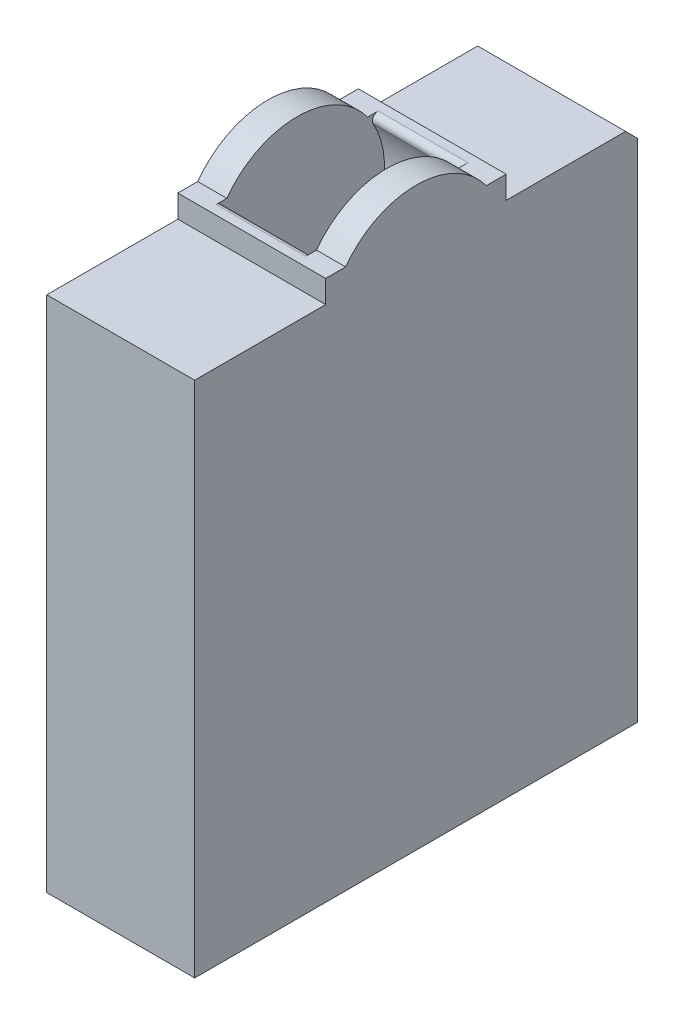
SolidWorks part; units mm, degrees
material "ABS"
ref_plane "Front Plane" through (0, 0, 0) normal (0, 0, 1) x (1, 0, 0)
ref_plane "Top Plane" through (0, 0, 0) normal (0, 1, 0) x (1, 0, 0)
ref_plane "Right Plane" through (0, 0, 0) normal (1, 0, 0) x (0, 0, -1)
sketch "Sketch1" plane through (0, 0, 0) normal (1, 0, 0) x (0, 0, -1)
  line L0 (-38, -92.7862) -> (-38, -3.8862)
  line L1 (-38, -3.8862) -> (-15.5, -3.8862)
  line L2 (-15.5, -3.8862) -> (-15.5, 0)
  line L3 (-15.5, 0) -> (15.5, 0)
  line L4 (15.5, 0) -> (15.5, -3.8862)
  line L5 (15.5, -3.8862) -> (38, -3.8862)
  line L6 (38, -3.8862) -> (38, -92.7862)
  line L7 (38, -92.7862) -> (-38, -92.7862)
  point P4 (0, 0)
  dimension "D1" = 88.9
  dimension "D2" = 3.8862
  dimension "D3" = 22.5
  dimension "D4" = 22.5
  dimension "D5" = 31
extrude "Boss-Extrude1" add sketch "Sketch1" along normal blind 25.4
sketch "Sketch2" plane through (25.4, 0, 0) normal (1, 0, 0) x (0, 0, -1)
  line L0 (-15.5, -3.8862) -> (15.5, -3.8862) construction
  line L1 (0, -3.8862) -> (0, 6.1138) construction
  line L2 (-12.0845, 0) -> (12.0845, 0)
  line L3 (15.5, 0) -> (-15.5, 0) construction
  arc A0 (12.0845, 0) -> (-12.0845, 0) centre (0, -8.8862) ccw
  dimension "D2" = 30
  dimension "D1" = 10
extrude "Boss-Extrude2" add sketch "Sketch2" against normal up to surface (25.4 mm away) up to face at (0, -25.1396, 0)
sketch "Sketch3" plane through (25.4, 0, 0) normal (1, 0, 0) x (0, 0, -1)
  circle A0 centre (0, -8.8862) radius 15
  arc A1 (12.0845, 0) -> (-12.0845, 0) centre (0, -8.8862) ccw construction
extrude "Cut-Extrude1" cut sketch "Sketch3" against normal offset from surface (15.4 mm away) 5 from offset 5 up to face at (0, -19.5003, 0) offset against normal yes
fillet "Fillet1" radius 1 2 edges at (12.7, 0, -12.0845) (12.7, 0, 12.0845)
sketch "Sketch4" plane through (0, 0, 0) normal (-1, 0, 0) x (0, 0, 1)
  line L0 (-12.0845, 0) -> (-19.4134, 8.7754)
  line L1 (-19.4134, 8.7754) -> (-13.9193, 13.3638)
  line L2 (-13.9193, 13.3638) -> (-6.5904, 4.5884)
  line L3 (-16.6663, 11.0696) -> (0, -8.8862) construction
  line L4 (-38, -3.8862) -> (-15.5, -3.8862) construction
  circle A0 centre (0, -8.8862) radius 15
  arc A1 (12.0845, 0) -> (-12.0845, 0) centre (0, -8.8862) ccw construction
  dimension "D1" = 17.25
  dimension "D2" = 26
  dimension "D3" = 7.1581
chamfer "Chamfer1" distance 2 angle 45 1 edges at (12.7, -3.8862, -38)
equation "\"D4@Sketch1\"=\"D3@Sketch1\""
